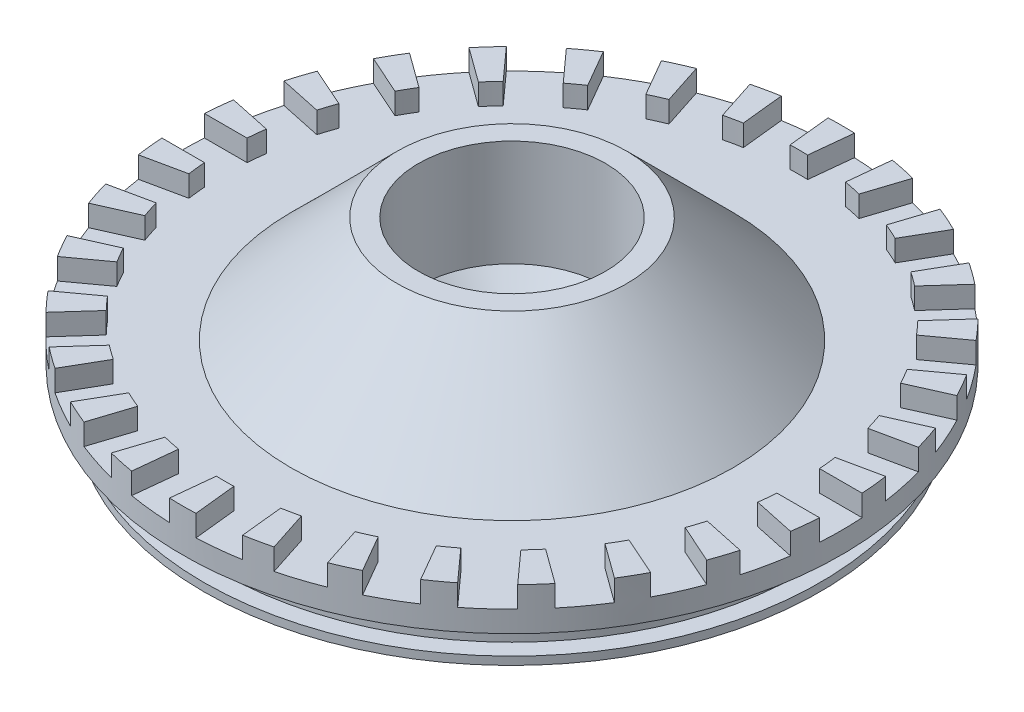
SolidWorks part; units mm, degrees
material "6061-T4 (SS)"
ref_plane "Front Plane" through (0, 0, 0) normal (0, 0, 1) x (1, 0, 0)
ref_plane "Top Plane" through (0, 0, 0) normal (0, 1, 0) x (1, 0, 0)
ref_plane "Right Plane" through (0, 0, 0) normal (1, 0, 0) x (0, 0, -1)
ref_axis "Axis1" through (0, -42.3, 0) along (0, 1, 0)
sketch "Sketch1" plane through (0, 0, 0) normal (0, 0, 1) x (1, 0, 0)
  line L0 (-7.62, 0) -> (-46.0375, 0)
  line L6 (-46.0375, 6.35) -> (-49.2125, 6.35)
  line L20 (-49.2125, 6.35) -> (-49.2125, 12.7)
  line L21 (-42.8625, 9.525) -> (-33.02, 9.525)
  line L22 (-46.0375, 0) -> (-46.0375, 1.2065)
  line L23 (-46.0375, 1.2065) -> (-43.4975, 1.2065)
  line L24 (-43.4975, 1.2065) -> (-43.4975, 4.7625)
  line L25 (-43.4975, 4.7625) -> (-46.0375, 4.7625)
  line L26 (-46.0375, 4.7625) -> (-46.0375, 6.35)
  line L27 (-7.62, 0) -> (-7.62, 3.175)
  line L28 (-7.62, 3.175) -> (-13.97, 9.525)
  line L29 (-13.97, 9.525) -> (-13.97, 25.4)
  line L30 (-13.97, 25.4) -> (-17.145, 25.4)
  line L32 (-7.62, 3.175) -> (-12.2413, 3.175) construction
  line L33 (-49.2125, 12.7) -> (-42.8625, 12.7)
  line L34 (-42.8625, 12.7) -> (-42.8625, 9.525)
  line L35 (-33.02, 9.525) -> (-17.145, 25.4)
  line L36 (-33.02, 9.525) -> (-25.5508, 9.525) construction
  dimension "D2" = 6.35
  dimension "D3" = 1.5875
  dimension "D4" = 2.54
  dimension "D5" = 3.556
  dimension "D6" = 3.175
  dimension "D7" = 3.175
  dimension "D8" = 6.35
  dimension "D9" = 45
  dimension "D10" = 3.175
  dimension "D11" = 3.175
  dimension "D12" = 6.35
  dimension "D13" = 46.0375
  dimension "D14" = 7.62
  dimension "D15" = 6.35
  dimension "D16" = 12.7
  dimension "D17" = 45
revolve "Revolve1" add sketch "Sketch1" angle 360 about axis through (0, -42.3, 0) along (0, 1, 0)
sketch "Sketch2" plane through (0, 12.7, 0) normal (0, 1, 0) x (1, 0, 0)
  line L0 (42.7447, 3.175) -> (55.4447, 3.175)
  line L1 (42.7447, -3.175) -> (55.4447, -3.175)
  line L2 (42.7447, 3.175) -> (42.7447, -3.175)
  line L3 (55.4447, 3.175) -> (55.4447, -3.175)
  circle A0 centre (0, 0) radius 42.8625 construction
  circle A2 centre (0, 0) radius 42.8625 construction
  point P10 (42.7447, 0)
  dimension "D1" = 6.35
  dimension "D2" = 12.7
extrude "Cut-Extrude1" cut sketch "Sketch2" against normal blind 3.175
pattern_circular "CirPattern1" count 30 over 360 about axis through (0, -42.3, 0) along (0, -1, 0) of "Cut-Extrude1" reverse direction yes
